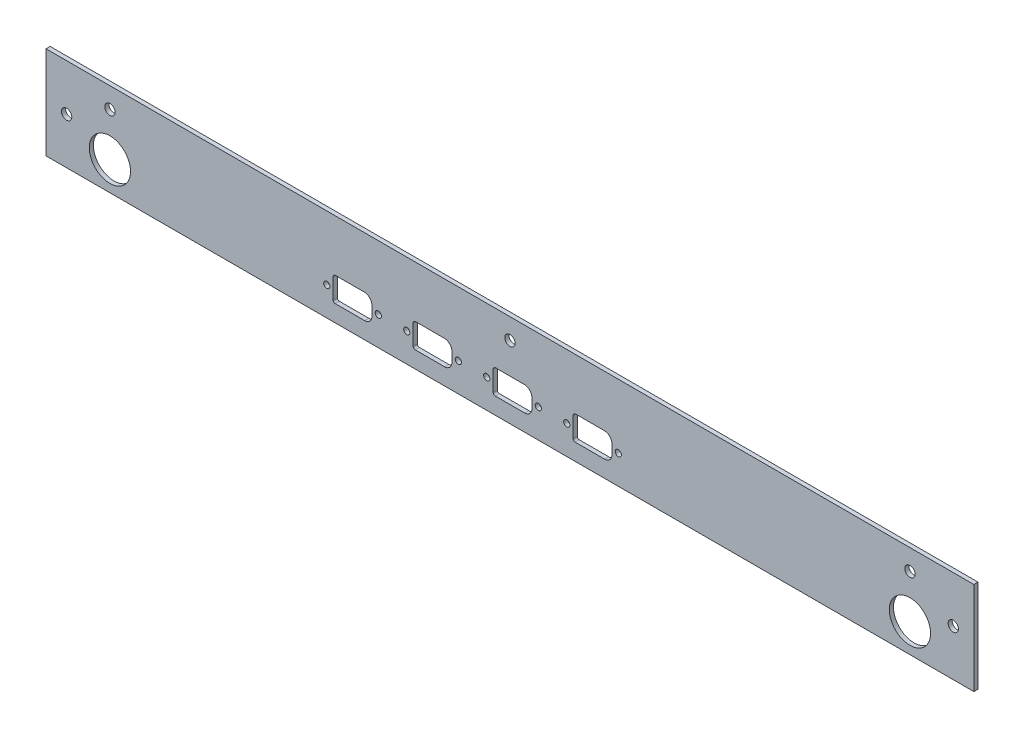
SolidWorks part; units mm, degrees
material "1345 Alloy"
ref_plane "Front Plane" through (0, 0, 0) normal (0, 0, 1) x (1, 0, 0)
ref_plane "Top Plane" through (0, 0, 0) normal (0, 1, 0) x (1, 0, 0)
ref_plane "Right Plane" through (0, 0, 0) normal (1, 0, 0) x (0, 0, -1)
sketch "Sketch1" plane through (0, 0, 0) normal (0, 0, 1) x (1, 0, 0)
  line L1 (-225, 22.5) -> (225, 22.5)
  line L2 (-225, 22.5) -> (-225, -22.5)
  line L3 (-225, -22.5) -> (225, -22.5)
  line L4 (225, 22.5) -> (225, -22.5)
  line L5 (-225, 22.5) -> (225, -22.5) construction
  line L6 (-225, -22.5) -> (225, 22.5) construction
  point P0 (0, 0)
  dimension "D1" = 450
  dimension "D2" = 45
extrude "Boss-Extrude1" add sketch "Sketch1" along normal blind 2
sketch "Sketch2" plane through (0, 0, 2) normal (0, 0, 1) x (1, 0, 0)
  line L0 (-28.1375, -8.55) -> (-25.0375, -8.55) construction
  line L1 (-31.6625, -14.4) -> (-45.9375, -14.4)
  line L2 (-45.7375, -2.5) -> (-31.8625, -2.5)
  line L3 (-46.9375, -13.4) -> (-46.9375, -3.7)
  line L4 (-28.1375, -10.875) -> (-28.1375, -6.225)
  line L5 (7.1375, -14.4) -> (-7.1375, -14.4)
  line L6 (-6.9375, -2.5) -> (6.9375, -2.5)
  line L7 (-8.1375, -13.4) -> (-8.1375, -3.7)
  line L8 (10.6625, -10.875) -> (10.6625, -6.225)
  line L9 (45.9375, -14.4) -> (31.6625, -14.4)
  line L10 (31.8625, -2.5) -> (45.7375, -2.5)
  line L11 (30.6625, -13.4) -> (30.6625, -3.7)
  line L12 (49.4625, -10.875) -> (49.4625, -6.225)
  line L17 (10.6625, -8.55) -> (13.7625, -8.55) construction
  line L18 (0, 22.5) -> (-225, 22.5) construction
  line L23 (-25.0375, -8.55) -> (-11.2375, -8.55) construction
  line L24 (-50.0375, -8.55) -> (-46.9375, -8.55) construction
  line L25 (-11.2375, -8.55) -> (-8.1375, -8.55) construction
  line L26 (27.5625, -8.55) -> (30.6625, -8.55) construction
  line L27 (-11.2375, -8.55) -> (-8.1375, -8.55) construction
  line L28 (13.7625, -8.55) -> (27.5625, -8.55) construction
  line L29 (49.4625, -8.55) -> (52.5625, -8.55) construction
  line L30 (-63.8375, -8.55) -> (-50.0375, -8.55) construction
  line L31 (-66.9375, -8.55) -> (-63.8375, -8.55) construction
  line L32 (0, -2.5) -> (0, 22.5) construction
  line L33 (-70.4625, -14.4) -> (-84.7375, -14.4)
  line L34 (-84.5375, -2.5) -> (-70.6625, -2.5)
  line L35 (-85.7375, -13.4) -> (-85.7375, -3.7)
  line L36 (-66.9375, -10.875) -> (-66.9375, -6.225)
  line L37 (-88.8375, -8.55) -> (-85.7375, -8.55) construction
  arc A0 (-28.1375, -10.875) -> (-31.6625, -14.4) centre (-31.6625, -10.875) cw
  arc A1 (-28.1375, -6.225) -> (-31.8625, -2.5) centre (-31.8625, -6.225) ccw
  arc A2 (-45.9375, -14.4) -> (-46.9375, -13.4) centre (-45.9375, -13.4) cw
  arc A3 (-46.9375, -3.7) -> (-45.7375, -2.5) centre (-45.7375, -3.7) cw
  arc A4 (10.6625, -10.875) -> (7.1375, -14.4) centre (7.1375, -10.875) cw
  arc A5 (10.6625, -6.225) -> (6.9375, -2.5) centre (6.9375, -6.225) ccw
  arc A6 (-7.1375, -14.4) -> (-8.1375, -13.4) centre (-7.1375, -13.4) cw
  arc A7 (-8.1375, -3.7) -> (-6.9375, -2.5) centre (-6.9375, -3.7) cw
  arc A8 (49.4625, -10.875) -> (45.9375, -14.4) centre (45.9375, -10.875) cw
  arc A9 (49.4625, -6.225) -> (45.7375, -2.5) centre (45.7375, -6.225) ccw
  arc A10 (31.6625, -14.4) -> (30.6625, -13.4) centre (31.6625, -13.4) cw
  arc A11 (30.6625, -3.7) -> (31.8625, -2.5) centre (31.8625, -3.7) cw
  circle A20 centre (-50.0375, -8.55) radius 1.5
  circle A21 centre (-25.0375, -8.55) radius 1.5
  circle A22 centre (-11.2375, -8.55) radius 1.5
  circle A23 centre (13.7625, -8.55) radius 1.5
  circle A24 centre (27.5625, -8.55) radius 1.5
  circle A25 centre (52.5625, -8.55) radius 1.5
  arc A26 (-66.9375, -10.875) -> (-70.4625, -14.4) centre (-70.4625, -10.875) cw
  arc A27 (-66.9375, -6.225) -> (-70.6625, -2.5) centre (-70.6625, -6.225) ccw
  arc A28 (-84.7375, -14.4) -> (-85.7375, -13.4) centre (-84.7375, -13.4) cw
  arc A29 (-85.7375, -3.7) -> (-84.5375, -2.5) centre (-84.5375, -3.7) cw
  circle A30 centre (-88.8375, -8.55) radius 1.5
  circle A31 centre (-63.8375, -8.55) radius 1.5
  dimension "D5" = 3
  dimension "D6" = 3
  dimension "D1" = 3
  dimension "D2" = 3
  dimension "D3" = 3
  dimension "D4" = 3
  dimension "D20" = 3
  dimension "D21" = 3
  dimension "D7" = 25
  dimension "D8" = 25
  dimension "D9" = 13.8
  dimension "D10" = 13.8
  dimension "D11" = 25
  dimension "D12" = 25
  dimension "D13" = 5.85
  dimension "D14" = 5.85
  dimension "D15" = 5.85
  dimension "D16" = 5.85
  dimension "D17" = 5.85
  dimension "D18" = 5.85
  dimension "D19" = 13.8
  dimension "D22" = 5.85
  dimension "D23" = 5.85
extrude "Cut-Extrude1" cut sketch "Sketch2" against normal through all
sketch "Sketch3" plane through (0, 0, 2) normal (0, 0, 1) x (1, 0, 0)
  line L0 (-225, 22.5) -> (-215, 22.5) construction
  line L1 (225, 22.5) -> (-225, 22.5) construction
  line L2 (-215, 22.5) -> (-215, 0) construction
  line L3 (225, -22.5) -> (225, 22.5) construction
  line L4 (-194, 12.4954) -> (194, 12.4954) construction
  line L5 (-225, 22.5) -> (-225, -22.5) construction
  line L7 (0, 22.5) -> (0, 12.5) construction
  circle A0 centre (-215, 0) radius 2.5
  circle A1 centre (215, 0) radius 2.5
  circle A2 centre (-194, 12.4954) radius 2.5
  circle A3 centre (194, 12.4954) radius 2.5
  circle A4 centre (0, 12.5) radius 2.5
  dimension "D3" = 5
  dimension "D6" = 5
  dimension "D7" = 5
  dimension "D8" = 5
  dimension "D9" = 5
  dimension "D1" = 10
  dimension "D2" = 22.5
  dimension "D4" = 2
  dimension "D5" = 10
  dimension "D10" = 10
  dimension "D11" = 31
  dimension "D12" = 31
extrude "Cut-Extrude2" cut sketch "Sketch3" against normal through all
sketch "Sketch4" plane through (0, 0, 2) normal (0, 0, 1) x (1, 0, 0)
  line L0 (-194, -8.55) -> (-194, -22.5) construction
  line L1 (-225, -22.5) -> (-194, -22.5) construction
  line L2 (194, -8.55) -> (194, -22.5) construction
  line L4 (194, -22.5) -> (225, -22.5) construction
  circle A0 centre (-194, -8.55) radius 10
  circle A1 centre (194, -8.55) radius 10
extrude "Cut-Extrude3" cut sketch "Sketch4" against normal blind 10
